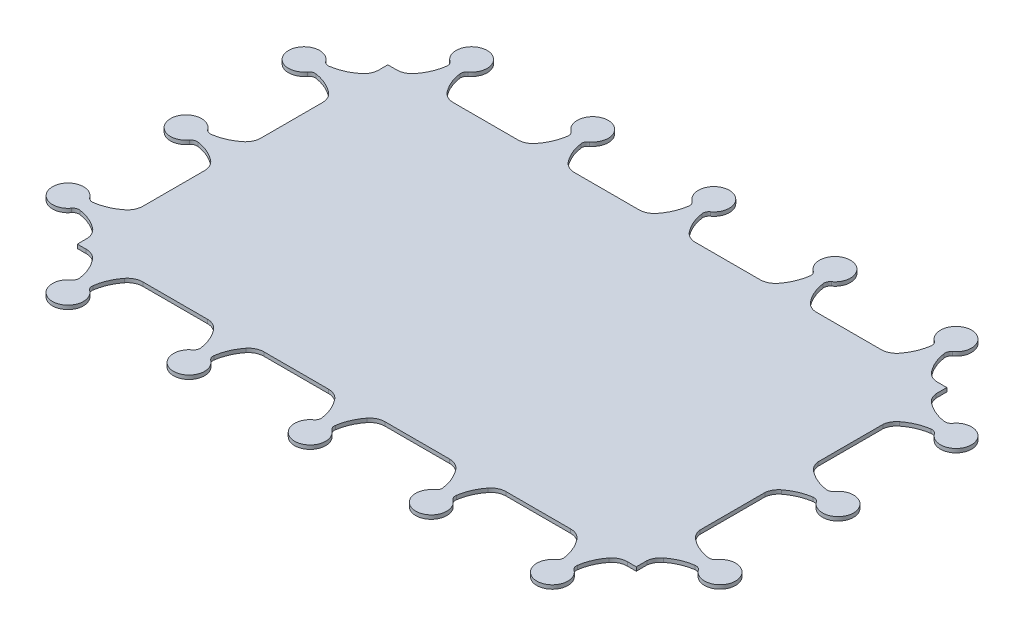
SolidWorks part; units mm, degrees
ref_plane "Front Plane" through (0, 0, 0) normal (0, 0, 1) x (1, 0, 0)
ref_plane "Top Plane" through (0, 0, 0) normal (0, 1, 0) x (1, 0, 0)
ref_plane "Right Plane" through (0, 0, 0) normal (1, 0, 0) x (0, 0, -1)
sketch "Sketch1" plane through (0, 0, 0) normal (0, 1, 0) x (1, 0, 0)
  line L0 (30.4307, 292.1) -> (30.4307, 270.947) construction
  line L1 (0, 0) -> (457.2, 0)
  line L2 (0, 0) -> (0, 254)
  line L3 (0, 254) -> (7.2682, 254)
  line L4 (457.2, 0) -> (457.2, 254)
  line L5 (53.5931, 254) -> (457.2, 254)
  line L6 (7.2682, 254) -> (53.5931, 254)
  line L7 (0, 254) -> (83.557, 170.443) construction
  arc A0 (17.2524, 258.851) -> (25.0143, 276.9904) centre (-12.7, 282.3981) ccw
  arc A1 (37.8914, 281.8225) -> (22.97, 281.8225) centre (30.4307, 292.1) ccw
  arc A2 (43.609, 258.851) -> (35.8471, 276.9904) centre (73.5614, 282.3981) cw
  arc A3 (35.8471, 276.9904) -> (37.8914, 281.8225) centre (40.8757, 277.7114) cw
  arc A4 (25.0143, 276.9904) -> (22.97, 281.8225) centre (19.9857, 277.7114) ccw
  arc A5 (43.609, 258.851) -> (53.5931, 254) centre (53.5931, 266.7) ccw
  arc A6 (17.2524, 258.851) -> (7.2682, 254) centre (7.2682, 266.7) cw
  arc A7 (-27.8225, 216.1086) -> (-27.8225, 231.03) centre (-38.1, 223.5693) cw
  arc A8 (-22.9904, 228.9857) -> (-27.8225, 231.03) centre (-23.7114, 234.0143) cw
  arc A9 (-22.9904, 218.1529) -> (-27.8225, 216.1086) centre (-23.7114, 213.1243) ccw
  arc A10 (-4.851, 210.391) -> (0, 200.4069) centre (-12.7, 200.4069) cw
  arc A11 (-4.851, 210.391) -> (-22.9904, 218.1529) centre (-28.3981, 180.4386) ccw
  arc A12 (-4.851, 236.7476) -> (-22.9904, 228.9857) centre (-28.3981, 266.7) cw
  arc A13 (-4.851, 236.7476) -> (0, 246.7318) centre (-12.7, 246.7318) ccw
  point P15 (35.5107, 280.4603)
  point P18 (25.3507, 280.4603)
  point P21 (48.1614, 254)
  point P24 (12.7, 254)
  dimension "D4" = 38.1
  dimension "D5" = 25.4
  dimension "D9" = 5.08
  dimension "D7" = 38.1
  dimension "D10" = 12.7
  dimension "D1" = 254
  dimension "D2" = 457.2
  dimension "D3" = 12.7
  dimension "D6" = 5.08
  dimension "D8" = 12.7
  dimension "D11" = 45
extrude "Boss-Extrude1" add sketch "Sketch1" along normal blind 3.175 contours L1 L4 L3 L2 region at (228.6, 0, -127)
extrude "Boss-Extrude2" add sketch "Sketch1<3>" along normal blind 3.175 contours L3 A2 A1 A0 region at (30.4307, 0, -278.2681)
sketch "Sketch1<3>" plane through (0, 0, 0) normal (0, 1, 0) x (1, 0, 0) same geometry as "Sketch1"
pattern_linear "LPattern1" count 5 spacing 99.06 along (1, 0, 0) of "Boss-Extrude2"
ref_plane "Plane1" through (0, 0, -127) normal (0, 0, 1) x (1, 0, 0)
mirror "Mirror1" about plane through (0, 0, -127) normal (0, 0, 1) of "LPattern1"
extrude "Boss-Extrude3" add sketch "Sketch1<4>" along normal blind 3.175 contours A13 A12 A8 A7 A9 A11 A10 L2 region at (-24.2681, 0, -223.5693)
sketch "Sketch1<4>" plane through (0, 0, 0) normal (0, 1, 0) x (1, 0, 0) same geometry as "Sketch1"
pattern_linear "LPattern2" count 3 spacing 96.52 along (0, 0, 1) of "Boss-Extrude3"
ref_plane "Plane2" through (228.5507, 0, 0) normal (1, 0, 0) x (0, 0, -1)
mirror "Mirror2" about plane through (228.5507, 0, 0) normal (1, 0, 0) of "LPattern2"
